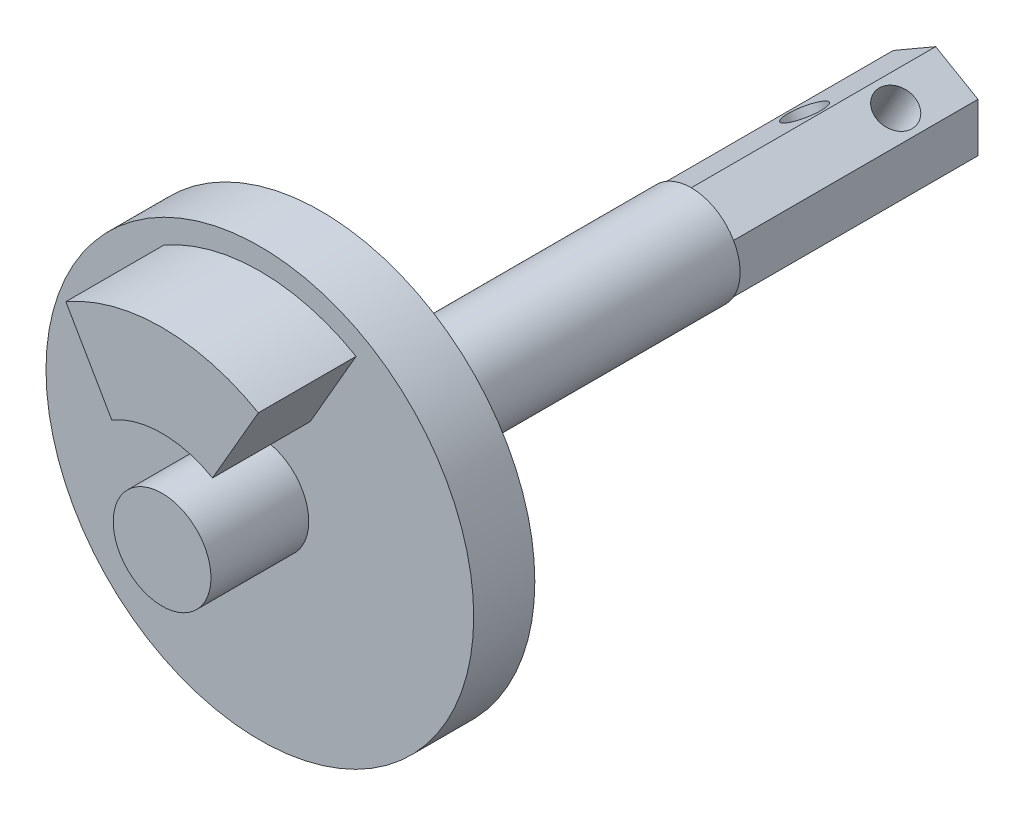
SolidWorks part; units mm, degrees
ref_plane "Front Plane" through (0, 0, 0) normal (0, 0, 1) x (1, 0, 0)
ref_plane "Top Plane" through (0, 0, 0) normal (0, 1, 0) x (1, 0, 0)
ref_plane "Right Plane" through (0, 0, 0) normal (1, 0, 0) x (0, 0, -1)
sketch "Sketch1" plane through (0, 0, 0) normal (0, 0, 1) x (1, 0, 0)
  circle A0 centre (0, 0) radius 17.5
  dimension "D1" = 35
extrude "Boss-Extrude1" add sketch "Sketch1" along normal mid plane 5
sketch "Sketch2" plane through (0, 0, 2.5) normal (0, 0, 1) x (1, 0, 0)
  line L3 (0, 0) -> (0, 11) construction
  line L4 (7.875, 13.6399) -> (4.125, 7.1447)
  line L5 (-4.125, 7.1447) -> (-7.875, 13.6399)
  arc A1 (4.125, 7.1447) -> (-4.125, 7.1447) centre (0, 0) ccw
  arc A6 (-7.875, 13.6399) -> (7.875, 13.6399) centre (0, 0) cw
  circle A7 centre (0, 0) radius 17.5 construction
  dimension "D2" = 7.5
  dimension "D3" = 1.75
  dimension "D1" = 30
extrude "Boss-Extrude2" add sketch "Sketch2" along normal blind 8
sketch "Sketch3" plane through (0, 0, 2.5) normal (0, 0, 1) x (1, 0, 0)
  circle A0 centre (0, 0) radius 4
extrude "Boss-Extrude3" add sketch "Sketch3" along normal blind 8
sketch "Sketch7" plane through (0, 0, -2.5) normal (0, 0, -1) x (-1, 0, 0)
  circle A0 centre (0, 0) radius 4
extrude "Boss-Extrude4" add sketch "Sketch7" along normal blind 30.3
sketch "Sketch9" plane through (0, 0, -32.8) normal (0, 0, -1) x (-1, 0, 0)
  line L0 (0, 4) -> (0, -4) construction
  line L1 (-3.4641, -2) -> (3.4641, 2) construction
  line L2 (-3.4641, 2) -> (3.4641, -2) construction
  line L11 (0, 4) -> (-3.4641, 2)
  line L12 (-3.4641, 2) -> (-3.4641, -2)
  line L13 (-3.4641, -2) -> (0, -4)
  line L14 (0, -4) -> (3.4641, -2)
  line L15 (3.4641, -2) -> (3.4641, 2)
  line L16 (3.4641, 2) -> (0, 4)
  circle A0 centre (0, 0) radius 4 construction
  point P4 (0, 0)
  point P5 (0, 0)
  point P6 (0, 0)
  point P8 (0, 0)
  point P9 (-3.1771, 1.941)
  point P11 (0, 0)
  point P13 (0, 0)
  point P15 (0, 0)
  point P19 (0, 0)
  point P22 (0, 0)
extrude "Boss-Extrude5" add sketch "Sketch9" along normal blind 20
sketch "Sketch10" plane through (-1.7321, -3, 0) normal (-0.5, -0.866, 0) x (0.866, -0.5, 0)
  line L2 (0, -47.8) -> (0, -32.8) construction
  line L3 (2, -32.8) -> (-2, -32.8) construction
  circle A0 centre (0, -47.8) radius 1.55
extrude "Cut-Extrude1" cut sketch "Sketch10" against normal up to surface (6.9282 mm away) up to face at (1.7321, 3, -42.8)
sketch "Sketch11" plane through (1.7321, -3, 0) normal (-0.5, 0.866, 0) x (0, 0, 1)
  line L0 (-43.8, 0) -> (-32.8, 0) construction
  line L1 (-32.8, 2) -> (-32.8, -2) construction
  circle A1 centre (-43.8, 0) radius 1.55
extrude "Cut-Extrude4" cut sketch "Sketch11" along normal up to surface (6.9282 mm away) up to face at (-1.7321, 3, -42.8)
